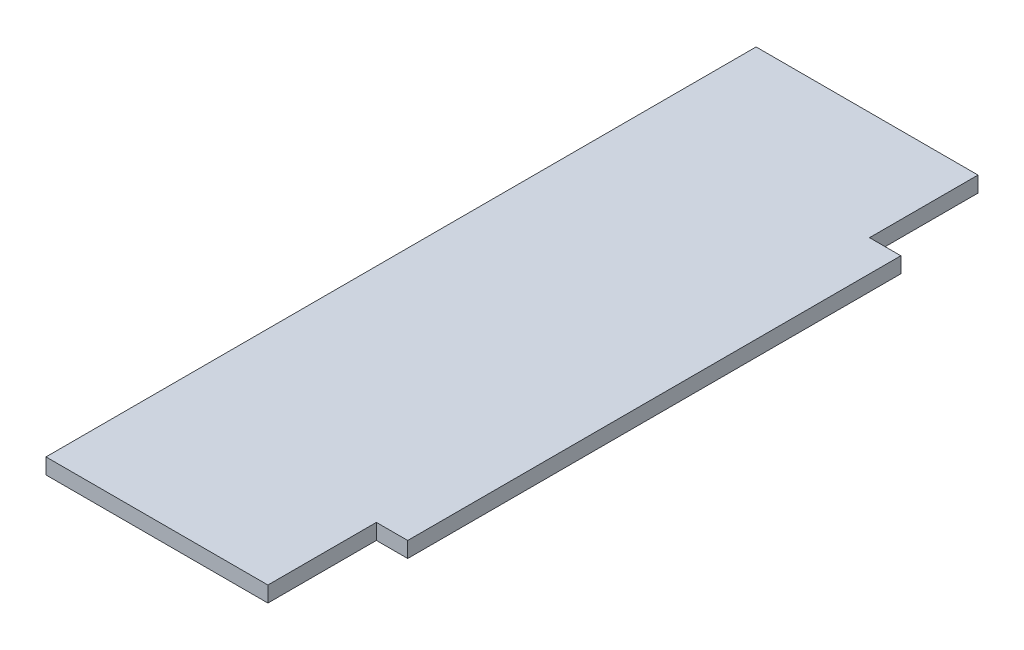
SolidWorks part; units mm, degrees
material "Cedar"
ref_plane "Front Plane" through (0, 0, 0) normal (0, 0, 1) x (1, 0, 0)
ref_plane "Top Plane" through (0, 0, 0) normal (0, 1, 0) x (1, 0, 0)
ref_plane "Right Plane" through (0, 0, 0) normal (1, 0, 0) x (0, 0, -1)
sketch "Sketch1" plane through (0, 0, 0) normal (0, 1, 0) x (1, 0, 0)
  line L0 (-22.5, 22) -> (22.5, 22)
  line L1 (22.5, 22) -> (22.5, 0)
  line L2 (22.5, 0) -> (28.85, 0)
  line L3 (28.85, 0) -> (28.85, -100)
  line L4 (28.85, -100) -> (22.5, -100)
  line L5 (22.5, -100) -> (22.5, -122)
  line L6 (22.5, -122) -> (-22.5, -122)
  line L7 (-22.5, -122) -> (-22.5, -100)
  line L8 (-22.5, -100) -> (-28.85, -100)
  line L9 (-28.85, -100) -> (-28.85, 0)
  line L10 (-28.85, 0) -> (-22.5, 0)
  line L11 (-22.5, 0) -> (-22.5, 22)
  line L12 (-22.5, 0) -> (-22.5, -100) construction
  point P11 (0, 22)
  point P14 (-28.85, -50)
  dimension "D1" = 6.35
  dimension "D2" = 100
  dimension "D3" = 45
  dimension "D4" = 144
extrude "Boss-Extrude1" add sketch "Sketch1" along normal blind 3.175 contours L11 L12 L7 L6 L5 L4 L3 L2 L1 L0 region at (2.2914, 0, 50)
equation "\"length\"= 144mm"
equation "\"w_mach\"= 45mm"
equation "\"w_tab\"= 100mm"
equation "\"t_wood\"= 0.125in"
equation "\"t_side\"= 0.25in"
equation "\"D1@Sketch1\"=\"t_side\""
equation "\"D2@Sketch1\"=\"w_tab\""
equation "\"D3@Sketch1\"=\"w_mach\""
equation "\"D4@Sketch1\"=\"length\""
equation "\"D1@Boss-Extrude1\"=\"t_wood\""
